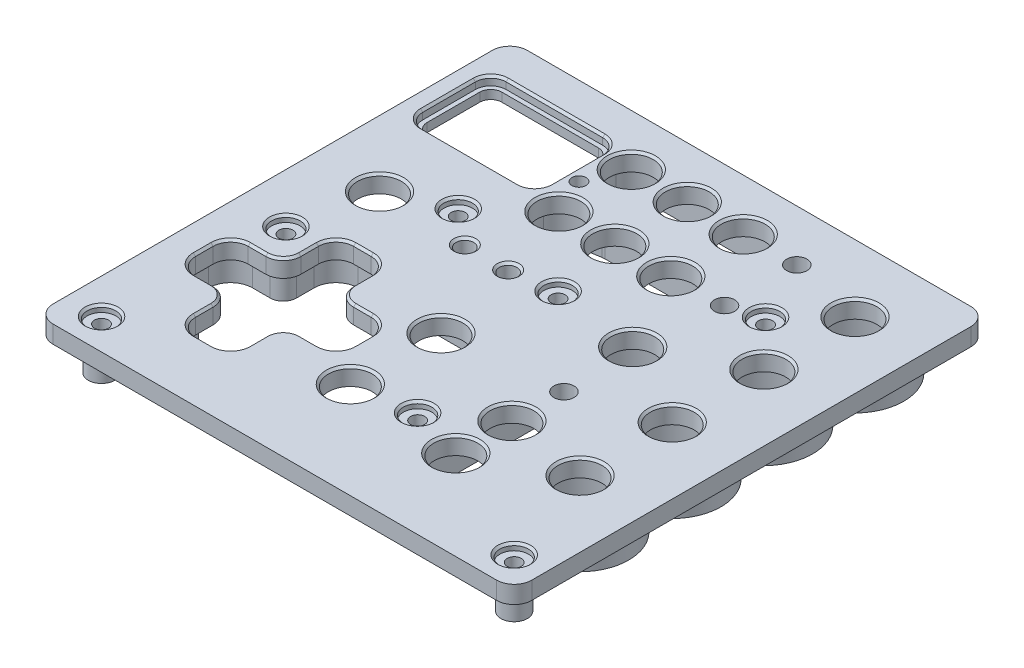
SolidWorks part; units mm, degrees
other "Markup1"
sketch "Sketch10" plane through (-33.0518, -8.9554, -52.6589) normal (-0.1076, -0.9941, -0.0133) x (0.4564, -0.0613, 0.8876)
ref_plane "Front Plane" through (0, 0, 0) normal (0, 0, 1) x (1, 0, 0)
ref_plane "Top Plane" through (0, 0, 0) normal (0, 1, 0) x (1, 0, 0)
ref_plane "Right Plane" through (0, 0, 0) normal (1, 0, 0) x (0, 0, -1)
sketch "Sketch1" plane through (0, 0, 0) normal (0, 1, 0) x (1, 0, 0)
  line L0 (32.6312, 56.5) -> (133.6312, 56.5)
  line L7 (137.6312, -47.5) -> (137.6312, 52.5)
  line L27 (28.6312, 52.5) -> (28.6312, -47.5)
  line L28 (28.6312, 52.5) -> (28.6312, -47.5)
  line L30 (32.6312, -51.5) -> (133.6312, -51.5)
  arc A0 (28.6312, -47.5) -> (32.6312, -51.5) centre (32.6312, -47.5) ccw
  arc A1 (133.6312, -51.5) -> (137.6312, -47.5) centre (133.6312, -47.5) ccw
  arc A2 (137.6312, 52.5) -> (133.6312, 56.5) centre (133.6312, 52.5) ccw
  arc A3 (32.6312, 56.5) -> (28.6312, 52.5) centre (32.6312, 52.5) ccw
  dimension "D2" = 4
  dimension "D1" = 5
extrude "Boss-Extrude1" add sketch "Sketch1" along normal blind 4
sketch "Sketch3" plane through (0, 4, 0) normal (0, 1, 0) x (1, 0, 0)
  line L44 (50.9951, -1.4499) -> (54.9951, -1.4499)
  line L45 (58.9951, -5.4499) -> (58.9951, -9.4499)
  line L46 (62.9951, -13.4499) -> (66.9951, -13.4499)
  line L47 (70.9951, -17.4499) -> (70.9951, -21.4499)
  line L48 (66.9951, -25.4499) -> (62.9951, -25.4499)
  line L49 (58.9951, -29.4499) -> (58.9951, -33.4499)
  line L50 (54.9951, -37.4499) -> (50.9951, -37.4499)
  line L51 (46.9951, -33.4499) -> (46.9951, -29.4499)
  line L52 (42.9951, -25.4499) -> (38.9951, -25.4499)
  line L53 (34.9951, -21.4499) -> (34.9951, -17.4499)
  line L54 (38.9951, -13.4499) -> (42.9951, -13.4499)
  line L55 (46.9951, -9.4499) -> (46.9951, -5.4499)
  circle A2 centre (122.5061, 41.25) radius 5
  circle A3 centre (122.5061, 20.5) radius 5
  circle A4 centre (122.5061, -0.375) radius 5
  circle A5 centre (122.5061, -21.375) radius 5
  circle A6 centre (103.9561, -18.35) radius 5
  circle A7 centre (103.1311, 10) radius 5
  circle A8 centre (78.5811, -9.125) radius 5
  circle A9 centre (78.3063, -29.5) radius 5
  circle A10 centre (43.6312, 11.8249) radius 5
  circle A11 centre (68.0062, 28.3001) radius 5
  circle A12 centre (80.7562, 28.3001) radius 5
  circle A13 centre (93.5062, 28.3001) radius 5
  circle A14 centre (93.5062, 44.8001) radius 5
  circle A15 centre (80.7562, 44.8001) radius 5
  circle A16 centre (68.0062, 44.8001) radius 5
  circle A17 centre (103.9561, -31.125) radius 5
  circle A18 centre (63.8812, 11.0001) radius 2
  circle A19 centre (73.7562, 10.9999) radius 2
  arc A20 (58.9951, -29.4499) -> (62.9951, -25.4499) centre (62.9951, -29.4499) cw
  arc A21 (62.9951, -13.4499) -> (58.9951, -9.4499) centre (62.9951, -9.4499) cw
  arc A22 (46.9951, -9.4499) -> (42.9951, -13.4499) centre (42.9951, -9.4499) cw
  arc A23 (46.9951, -29.4499) -> (42.9951, -25.4499) centre (42.9951, -29.4499) ccw
  arc A24 (70.9951, -17.4499) -> (66.9951, -13.4499) centre (66.9951, -17.4499) ccw
  arc A25 (58.9951, -5.4499) -> (54.9951, -1.4499) centre (54.9951, -5.4499) ccw
  arc A26 (50.9951, -1.4499) -> (46.9951, -5.4499) centre (50.9951, -5.4499) ccw
  arc A27 (38.9951, -13.4499) -> (34.9951, -17.4499) centre (38.9951, -17.4499) ccw
  arc A28 (34.9951, -21.4499) -> (38.9951, -25.4499) centre (38.9951, -21.4499) ccw
  arc A29 (46.9951, -33.4499) -> (50.9951, -37.4499) centre (50.9951, -33.4499) ccw
  arc A30 (54.9951, -37.4499) -> (58.9951, -33.4499) centre (54.9951, -33.4499) ccw
  arc A31 (66.9951, -25.4499) -> (70.9951, -21.4499) centre (66.9951, -21.4499) ccw
  circle A32 centre (105.6344, 44.8749) radius 2.3
  circle A33 centre (105.4147, 28.6249) radius 2.3
  circle A34 centre (104.1313, -6.6735) radius 2.3
  point P54 (58.9951, -13.4499)
  dimension "D1" = 4
  dimension "D2" = 4
extrude "Cut-Extrude2" cut sketch "Sketch3" against normal through all
sketch "Sketch11" plane through (0, 4, 0) normal (0, 1, 0) x (1, 0, 0)
  line L0 (61.4355, 44.8615) -> (61.4355, 32.8615)
  line L4 (32.4355, 32.8615) -> (32.4355, 44.8615)
  line L6 (35.9355, 48.3615) -> (57.9355, 48.3615)
  line L8 (61.4355, 44.8615) -> (61.4355, 32.8615)
  line L9 (57.9355, 29.3615) -> (35.9355, 29.3615)
  line L10 (32.4355, 32.8615) -> (32.4355, 44.8615)
  line L11 (35.9355, 48.3615) -> (57.9355, 48.3615)
  line L13 (57.9355, 29.3615) -> (35.9355, 29.3615)
  arc A0 (57.9355, 29.3615) -> (61.4355, 32.8615) centre (57.9355, 32.8615) ccw
  arc A1 (32.4355, 32.8615) -> (35.9355, 29.3615) centre (35.9355, 32.8615) ccw
  arc A2 (35.9355, 48.3615) -> (32.4355, 44.8615) centre (35.9355, 44.8615) ccw
  arc A3 (61.4355, 44.8615) -> (57.9355, 48.3615) centre (57.9355, 44.8615) ccw
  arc A4 (57.9355, 29.3615) -> (61.4355, 32.8615) centre (57.9355, 32.8615) ccw
  arc A5 (32.4355, 32.8615) -> (35.9355, 29.3615) centre (35.9355, 32.8615) ccw
  arc A6 (35.9355, 48.3615) -> (32.4355, 44.8615) centre (35.9355, 44.8615) ccw
  arc A7 (61.4355, 44.8615) -> (57.9355, 48.3615) centre (57.9355, 44.8615) ccw
extrude "Cut-Extrude8" cut sketch "Sketch11" against normal blind 2
sketch "Sketch12" plane through (0, 2, 0) normal (0, 1, 0) x (1, 0, 0)
  line L4 (57.9355, 47.3615) -> (35.9355, 47.3615)
  line L5 (57.9355, 47.3615) -> (35.9355, 47.3615)
  line L6 (33.4355, 44.8615) -> (33.4355, 32.8615)
  line L7 (33.4355, 44.8615) -> (33.4355, 32.8615)
  line L8 (35.9355, 30.3615) -> (57.9355, 30.3615)
  line L9 (35.9355, 30.3615) -> (57.9355, 30.3615)
  line L10 (60.4355, 32.8615) -> (60.4355, 44.8615)
  line L11 (60.4355, 32.8615) -> (60.4355, 44.8615)
  arc A4 (60.4355, 44.8615) -> (57.9355, 47.3615) centre (57.9355, 44.8615) ccw
  arc A5 (60.4355, 44.8615) -> (57.9355, 47.3615) centre (57.9355, 44.8615) ccw
  arc A6 (35.9355, 47.3615) -> (33.4355, 44.8615) centre (35.9355, 44.8615) ccw
  arc A7 (35.9355, 47.3615) -> (33.4355, 44.8615) centre (35.9355, 44.8615) ccw
  arc A8 (33.4355, 32.8615) -> (35.9355, 30.3615) centre (35.9355, 32.8615) ccw
  arc A9 (33.4355, 32.8615) -> (35.9355, 30.3615) centre (35.9355, 32.8615) ccw
  arc A10 (57.9355, 30.3615) -> (60.4355, 32.8615) centre (57.9355, 32.8615) ccw
  arc A11 (57.9355, 30.3615) -> (60.4355, 32.8615) centre (57.9355, 32.8615) ccw
  dimension "D1" = 1
extrude "Cut-Extrude9" cut sketch "Sketch12" against normal through all
sketch "Sketch13" plane through (0, 0, 0) normal (0, -1, 0) x (1, 0, 0)
  line L0 (133.6312, -52.5) -> (28.6312, -52.5) construction
  line L2 (112.3813, -52.5) -> (112.3813, -45.8327)
  line L4 (61.3813, -52.5) -> (61.3813, -21.5)
  line L5 (68.0062, -22.3001) -> (106.5062, -22.3001)
  line L7 (68.0062, -51.3001) -> (106.5062, -51.3001)
  line L8 (110.5062, -47.3001) -> (110.5062, -42.8001)
  line L10 (68.0062, -38.8001) -> (106.5062, -38.8001)
  line L12 (110.5062, -34.3001) -> (110.5062, -26.3001)
  line L14 (92.0062, -10.073) -> (92.0062, -16.5)
  line L16 (96.9561, 31.125) -> (96.9561, 6.3677)
  line L17 (110.9561, 6.3677) -> (110.9561, 31.125)
  line L18 (94.9561, 31.125) -> (94.9561, 6.3677)
  line L20 (112.9561, 27.11) -> (112.9561, 31.125)
  line L22 (112.9561, 6.3677) -> (112.9561, 31.125) construction
  line L58 (49.0951, -3.4501) -> (56.6951, -3.4501)
  line L64 (51.4145, 42.1499) -> (49.0951, 42.1499)
  line L65 (42.0951, 35.1499) -> (42.0951, 31.1499)
  line L66 (41.0951, 30.1499) -> (37.0951, 30.1499)
  line L67 (30.0951, 23.1499) -> (30.0951, 15.5499)
  line L68 (37.0951, 8.5499) -> (41.0951, 8.5499)
  line L69 (42.0951, 7.5499) -> (42.0951, 3.5499)
  line L78 (87, 41.2148) -> (87, 1.6203)
  line L80 (87, 41.2148) -> (81.1395, 41.2148)
  line L90 (80.1354, -3.1952) -> (60.3806, -3.1952)
  line L91 (60.3806, -3.1952) -> (56.6951, -3.4501)
  line L92 (81.1395, 41.2148) -> (80.9453, 41.2148)
  line L98 (78.4256, -1.1952) -> (60.3115, -1.1952)
  line L99 (60.3115, -1.1952) -> (56.626, -1.4501)
  line L100 (49.0951, -1.4501) -> (56.626, -1.4501)
  line L101 (44.0951, 7.5499) -> (44.0951, 3.5499)
  line L102 (37.0951, 10.5499) -> (41.0951, 10.5499)
  line L103 (32.0951, 23.1499) -> (32.0951, 15.5499)
  line L104 (41.0951, 28.1499) -> (37.0951, 28.1499)
  line L105 (44.0951, 35.1499) -> (44.0951, 31.1499)
  line L106 (56.6951, 40.1499) -> (49.0951, 40.1499)
  line L112 (88.0062, -20.5) -> (61.3813, -20.5)
  line L113 (61.3813, -20.5) -> (61.3813, -21.5)
  line L114 (110.5062, -34.3001) -> (110.5062, -35.3001)
  line L115 (110.5062, -35.3001) -> (71.526, -35.3001)
  line L117 (72.1395, 36.8974) -> (59.4553, 39.319) construction
  line L118 (81.8089, 36.8974) -> (72.1395, 36.8974) construction
  line L119 (72.3287, 38.8974) -> (60.1904, 41.2148) construction
  line L120 (79.8089, 38.8974) -> (72.3287, 38.8974) construction
  line L122 (85, 39.2148) -> (85, 0.6001) construction
  line L123 (85, 39.2148) -> (81.8089, 39.2148) construction
  line L124 (81.8089, 39.2148) -> (81.8089, 36.8974) construction
  line L126 (81.8089, 39.2148) -> (81.8089, 39.2148) construction
  line L127 (85, 0.6001) -> (78.6937, 0.6001) construction
  line L128 (85, 0.6001) -> (85, 0.6001) construction
  line L129 (85, 4.6001) -> (85, 35.9119)
  line L130 (85, 4.6001) -> (85, 4.3183)
  line L135 (61.3813, -52.5) -> (112.3813, -52.5)
  line L136 (56.6951, 42.1499) -> (49.0951, 42.1499) construction
  line L137 (81.7885, 39.1911) -> (60.1254, 39.1911)
  line L138 (79.8089, 41.2148) -> (79.8089, 38.8974) construction
  line L139 (60.7768, 41.1028) -> (72.9994, 41.1028)
  line L143 (81.1395, 41.2148) -> (79.8089, 41.2148) construction
  line L144 (81.2306, -3.0424) -> (84.0953, -2.2268)
  line L145 (82.4501, -0.032) -> (82.3087, -0.1438)
  line L146 (80.3612, -0.9707) -> (78.9594, -1.1595)
  line L147 (78.6937, -1.1952) -> (60.3115, -1.1952) construction
  line L148 (78.6937, 0.6001) -> (78.6937, -1.1952) construction
  line L149 (85.6449, -1.3999) -> (80.6937, -1.3999) construction
  line L150 (87, -1.3999) -> (85.6449, -1.3999) construction
  line L151 (80.6937, -1.3999) -> (80.6937, -3.1952) construction
  line L152 (80.6937, -3.1952) -> (60.3806, -3.1952) construction
  line L153 (87, 41.2148) -> (87, -1.3999) construction
  line L154 (68.272, -34.8415) -> (70.9104, -35.2525)
  arc A5 (68.0062, -38.8001) -> (62.3939, -46.9221) centre (68.0062, -44.8001) ccw
  arc A7 (68.0062, -51.3001) -> (62.3939, -46.9221) centre (68.0062, -45.5139) cw
  circle A8 centre (122.5061, -41.25) radius 10
  circle A9 centre (122.5061, -20.5) radius 10
  circle A10 centre (122.5061, 0.4029) radius 10
  circle A11 centre (103.1311, -10) radius 10
  circle A12 centre (122.5061, 21.375) radius 10
  arc A15 (130.5136, 13.6801) -> (112.9561, 27.11) centre (122.506, 21.4032) ccw
  arc A16 (105.5959, 0.8487) -> (101.7697, 1.0416) centre (103.1311, -10) ccw
  arc A20 (130.5579, -7.2746) -> (130.5137, 8.1264) centre (122.5061, 0.4029) ccw
  arc A21 (130.6014, -28.1036) -> (130.5579, -12.7952) centre (122.5062, -20.4724) ccw
  arc A25 (112.3813, -45.8327) -> (130.6014, -33.5912) centre (122.5062, -41.2224) ccw
  arc A26 (110.9561, 31.125) -> (96.9561, 31.125) centre (103.9561, 31.125) ccw
  arc A28 (96.9561, 6.3677) -> (97.7122, 3.2032) centre (103.9561, 6.3677) ccw
  arc A29 (112.9561, 31.125) -> (94.9561, 31.125) centre (103.9561, 31.125) ccw
  arc A30 (94.9561, 6.3677) -> (95.8988, 2.3578) centre (103.9561, 6.3677) ccw
  arc A34 (109.8501, 2.5914) -> (110.9561, 6.3677) centre (103.9561, 6.3677) ccw
  arc A35 (94.9561, 6.3677) -> (112.9561, 6.3677) centre (103.9561, 6.3677) ccw construction
  arc A36 (95.1775, -2.2212) -> (92.0062, -10.073) centre (103.1311, -10) ccw
  arc A37 (96.9561, 6.3677) -> (110.9561, 6.3677) centre (103.9561, 6.3677) ccw construction
  arc A76 (42.0951, 3.5499) -> (49.0951, -3.4501) centre (49.0951, 3.5499) ccw
  arc A82 (59.7699, 41.4384) -> (56.6951, 42.1499) centre (56.6951, 35.1499) ccw
  arc A83 (49.0951, 42.1499) -> (42.0951, 35.1499) centre (49.0951, 35.1499) ccw
  arc A84 (41.0951, 30.1499) -> (42.0951, 31.1499) centre (41.0951, 31.1499) ccw
  arc A85 (37.0951, 30.1499) -> (30.0951, 23.1499) centre (37.0951, 23.1499) ccw
  arc A86 (30.0951, 15.5499) -> (37.0951, 8.5499) centre (37.0951, 15.5499) ccw
  arc A87 (42.0951, 7.5499) -> (41.0951, 8.5499) centre (41.0951, 7.5499) ccw
  arc A90 (44.0951, 3.5499) -> (49.0951, -1.4501) centre (49.0951, 3.5499) ccw
  arc A91 (44.0951, 7.5499) -> (41.0951, 10.5499) centre (41.0951, 7.5499) ccw
  arc A92 (32.0951, 15.5499) -> (37.0951, 10.5499) centre (37.0951, 15.5499) ccw
  arc A93 (37.0951, 28.1499) -> (32.0951, 23.1499) centre (37.0951, 23.1499) ccw
  arc A94 (41.0951, 28.1499) -> (44.0951, 31.1499) centre (41.0951, 31.1499) ccw
  arc A95 (49.0951, 40.1499) -> (44.0951, 35.1499) centre (49.0951, 35.1499) ccw
  arc A96 (59.0175, 39.5778) -> (56.6951, 40.1499) centre (56.6951, 35.1499) ccw
  arc A97 (88.0062, -20.5) -> (92.0062, -16.5) centre (88.0062, -16.5) ccw
  arc A98 (130.5136, 13.6801) -> (130.5137, 8.1264) centre (133.3928, 10.9033) ccw
  arc A99 (130.6014, -28.1036) -> (130.6014, -33.5912) centre (133.512, -30.8474) ccw
  arc A100 (130.5579, -7.2746) -> (130.5579, -12.7952) centre (133.4528, -10.0349) ccw
  arc A101 (105.5959, 0.8487) -> (109.8501, 2.5914) centre (106.4821, 4.7493) ccw
  arc A102 (101.7697, 1.0416) -> (97.7122, 3.2032) centre (101.2802, 5.0115) cw
  arc A103 (106.5062, -51.3001) -> (110.5062, -47.3001) centre (106.5062, -47.3001) ccw
  arc A104 (106.5062, -38.8001) -> (110.5062, -42.8001) centre (106.5062, -42.8001) cw
  arc A105 (106.5062, -22.3001) -> (110.5062, -26.3001) centre (106.5062, -26.3001) cw
  arc A107 (59.4553, 39.319) -> (56.6951, 40.1499) centre (56.6951, 35.1499) ccw construction
  arc A108 (59.0175, 39.5778) -> (60.1254, 39.1911) centre (60.8755, 43.1201) ccw
  arc A109 (60.1904, 41.2148) -> (56.6951, 42.1499) centre (56.6951, 35.1499) ccw construction
  arc A110 (59.7699, 41.4384) -> (60.7768, 41.1028) centre (61.527, 45.0318) ccw
  arc A112 (95.8988, 2.3578) -> (95.1775, -2.2212) centre (92.3178, 0.5756) cw
  arc A113 (85, 35.9119) -> (81.7885, 39.1911) centre (83.5458, 37.6999) ccw
  arc A115 (83.8131, 0.6711) -> (85.1693, 3.167) centre (83.2539, 2.5914) ccw
  arc A116 (85.1693, 3.167) -> (85, 4.3183) centre (89, 4.3183) cw
  arc A117 (56.6951, 42.1499) -> (55.6799, 42.0189) centre (56.6951, 38.1499) ccw
  arc A118 (51.4145, 42.1499) -> (52.8417, 41.8866) centre (51.4145, 38.1499) cw
  arc A119 (52.8417, 41.8866) -> (55.6799, 42.0189) centre (54.1092, 45.2051) ccw
  arc A120 (74.7448, 40.7019) -> (72.9994, 41.1028) centre (72.9994, 37.1028) ccw
  arc A121 (74.7448, 40.7019) -> (79.0991, 40.7632) centre (76.8609, 45.0653) ccw
  arc A122 (80.9453, 41.2148) -> (79.0991, 40.7632) centre (80.9453, 37.2148) ccw
  arc A123 (78.9594, -1.1595) -> (78.4256, -1.1952) centre (78.4256, 2.8048) cw
  arc A124 (82.3087, -0.1438) -> (80.3612, -0.9707) centre (79.8274, 2.9935) cw
  arc A125 (83.8131, 0.6711) -> (82.4501, -0.032) centre (84.9315, -3.1693) ccw
  arc A126 (81.2306, -3.0424) -> (80.1354, -3.1952) centre (80.1354, 0.8048) cw
  arc A127 (87, 1.6203) -> (84.0953, -2.2268) centre (83, 1.6203) cw
  arc A128 (67.7993, -34.7964) -> (62.3939, -30.4221) centre (68.0062, -29.0139) cw
  arc A129 (68.0062, -22.3001) -> (62.3939, -30.4221) centre (68.0062, -28.3001) ccw
  arc A130 (71.526, -35.3001) -> (70.9104, -35.2525) centre (71.526, -31.3001) cw
  arc A131 (68.272, -34.8415) -> (67.7993, -34.7964) centre (67.6564, -38.7939) ccw
  point P139 (56.6951, 3.5499)
  point P140 (63.6951, 3.5499)
  point P144 (68.6951, 8.5499)
  point P145 (68.6951, 15.5499)
  point P146 (75.6951, 15.5499)
  point P153 (63.6951, 35.1499)
  dimension "D3" = 4
  dimension "D1" = 4
  dimension "D4" = 4
  dimension "D5" = 4
  dimension "D6" = 4
  dimension "D7" = 4
  dimension "D8" = 4
  dimension "D9" = 4
  dimension "D10" = 4
  dimension "D11" = 4
  dimension "D12" = 4
  dimension "D13" = 4
  dimension "D14" = 4
  dimension "D15" = 4
  dimension "D16" = 4
  dimension "D17" = 4
  dimension "D2" = 51
extrude "Boss-Extrude2" add sketch "Sketch13" along normal blind 7.1
sketch "Sketch14" plane through (0, -7.1, 0) normal (0, -1, 0) x (1, 0, 0)
  line L0 (110.9561, 31.125) -> (110.9561, 40.2144)
  line L5 (110.9561, 40.2144) -> (106.9561, 40.2144)
  line L7 (106.9561, 31.125) -> (110.9561, 31.125)
  line L8 (106.9561, 31.125) -> (96.9561, 31.125)
  line L9 (96.9561, 31.125) -> (96.9561, 40.2144)
  line L10 (96.9561, 40.2144) -> (106.9561, 40.2144)
extrude "Cut-Extrude10" cut sketch "Sketch14" against normal blind 1.5
sketch "Sketch8" plane through (0, 4, 0) normal (0, -1, 0) x (-1, 0, 0)
  circle A0 centre (-36.6312, -44.5) radius 1.6
  circle A1 centre (-91.6312, -27.5) radius 1.6
  circle A2 centre (-39.8812, -5.75) radius 1.6
  circle A3 centre (-56.0062, 17.375) radius 1.6
  circle A4 centre (-64.3812, 36.5) radius 1.6
  circle A5 centre (-83.6312, 12.5) radius 1.6
  circle A6 centre (-112.3812, 31) radius 1.6
  circle A7 centre (-130.6312, -44.5) radius 1.6
extrude "Cut-Extrude7" cut sketch "Sketch8" along normal through all
sketch "Sketch16" plane through (0, 0, 0) normal (0, -1, 0) x (1, 0, 0)
  line L1 (37.0951, 8.5499) -> (41.0951, 8.5499) construction
  line L3 (40.9586, 8.5499) -> (41.0951, 8.5499)
  line L4 (87, 1.6203) -> (87, 41.2148) construction
  line L5 (94.9561, 31.125) -> (94.9561, 6.3677) construction
  line L6 (87, 24.5) -> (87, 30.5)
  line L7 (94.9561, 30.5) -> (94.9561, 24.5)
  line L8 (91.6312, 24.5) -> (87, 24.5)
  line L9 (91.6312, 30.5) -> (87, 30.5)
  line L10 (91.6312, 30.5) -> (94.9561, 30.5)
  line L11 (91.6312, 24.5) -> (94.9561, 24.5)
  circle A0 centre (36.6312, 44.5) radius 3
  arc A1 (40.9586, 8.5499) -> (42.0601, 7.8121) centre (39.8812, 5.75) ccw
  circle A2 centre (56.0062, -17.375) radius 3
  circle A4 centre (130.6312, 44.5) radius 3
  circle A5 centre (83.6312, -12.5) radius 3
  arc A6 (42.0951, 7.5499) -> (41.0951, 8.5499) centre (41.0951, 7.5499) ccw construction
  arc A7 (42.0601, 7.8121) -> (41.0951, 8.5499) centre (41.0951, 7.5499) ccw
fillet "Fillet1" radius 4 1 edges at (110.5062, -3.55, -35.3001)
fillet "Fillet2" radius 4 1 edges at (112.9561, -3.55, 27.11)
fillet "Fillet3" radius 4 rebuild error yes
fillet "Fillet4" radius 4 rebuild error yes
fillet "Fillet5" radius 4 1 edges at (112.3813, -3.55, -45.8327)
sketch "Sketch15" plane through (0, 4, 0) normal (0, 1, 0) x (1, 0, 0)
  circle A0 centre (56.0062, 17.375) radius 3.25
  circle A1 centre (39.8812, -5.75) radius 3.25
  circle A2 centre (36.6312, -44.5) radius 3.25
  circle A3 centre (91.6312, -27.5) radius 3.25
  circle A4 centre (130.6312, -44.5) radius 3.25
  circle A5 centre (112.3812, 31) radius 3.25
  circle A6 centre (83.6312, 12.5) radius 3.25
extrude "Cut-Extrude11" cut sketch "Sketch15" against normal blind 1.5
chamfer "Chamfer1" distance 0.5 angle 45 57 edges at (93.5062, 4, -39.8001) (80.7562, 4, -39.8001) (68.0062, 4, -39.8001) (63.8812, 4, -9.0001) (73.7562, 4, -8.9999) (83.6312, 4, -9.25) (56.0062, 4, -14.125) (43.6312, 4, -6.8249) (39.8812, 4, 9) (36.6312, 4, 47.75) (52.9951, 4, 37.4499) (46.9951, 4, 31.4499) (45.8235, 4, 26.6215) (40.9951, 4, 25.4499) (34.9951, 4, 19.4499) (40.9951, 4, 13.4499) (45.8235, 4, 12.2783) (46.9951, 4, 7.4499) (52.9951, 4, 1.4499) (58.9951, 4, 31.4499) (58.9951, 4, 7.4499) (60.1667, 4, 26.6215) (60.1667, 4, 12.2783) (64.9951, 4, 25.4499) (70.9951, 4, 19.4499) (64.9951, 4, 13.4499) (78.5811, 4, 14.125) (78.3063, 4, 34.5) (130.6312, 4, 47.75) (91.6312, 4, 30.75) (103.9561, 4, 36.125) (103.9561, 4, 23.35) (122.5061, 4, 26.375) (122.5061, 4, 5.375) (103.1311, 4, -5) (122.5061, 4, -15.5) (112.3812, 4, -27.75) (93.5062, 4, -23.3001) (80.7562, 4, -23.3001) (68.0062, 4, -23.3001) (32.4355, 4, -38.8615) (61.4355, 4, -38.8615) (46.9355, 4, -29.3615) (60.4103, 4, -30.3866) (33.4606, 4, -30.3866) (60.4103, 4, -47.3364) (33.4606, 4, -47.3364) (46.9355, 4, -48.3615) (122.5061, 4, -36.25) (36.1667, 4, 24.2783) (48.1667, 4, 36.2783) (36.1667, 4, 14.6215) (57.8235, 4, 36.2783) (48.1667, 4, 2.6215) (69.8235, 4, 24.2783) (57.8235, 4, 2.6215) (69.8235, 4, 14.6215)
fillet "Fillet6" radius 4 rebuild error yes
fillet "Fillet9" radius 4 rebuild error yes
fillet "Fillet10" radius 3 2 edges at (87, -3.55, 41.2148) (87, -3.55, 1.6203)
fillet "Fillet11" radius 3 rebuild error yes
fillet "Fillet12" radius 3 rebuild error yes
extrude "Boss-Extrude4" add sketch "Sketch16" along normal up to surface (7.1 mm away) up to face at (112.3812, -7.1, -32.6)
sketch "Sketch17" plane through (0, 0, 0) normal (0, 1, 0) x (1, 0, 0)
  circle A0 centre (36.6312, -44.5) radius 1.6
  circle A1 centre (39.8812, -5.75) radius 1.6
  circle A2 centre (56.0062, 17.375) radius 1.6
  circle A3 centre (83.6312, 12.5) radius 1.6
  circle A4 centre (91.6312, -27.5) radius 1.6
  circle A6 centre (130.6312, -44.5) radius 1.6
extrude "Cut-Extrude12" cut sketch "Sketch17" against normal through all
fillet "Fillet13" radius 2 9 edges at (94.9561, -3.55, 30.5) (87, -3.55, 30.5) (94.9561, -3.55, 24.5) (87, -3.55, 24.5) (38.8039, -3.55, 8.5499) (42.0951, -3.55, 3.7255) (61.3813, -3.55, -20.5) (112.3813, -3.55, -52.5) (61.3813, -3.55, -52.5)
